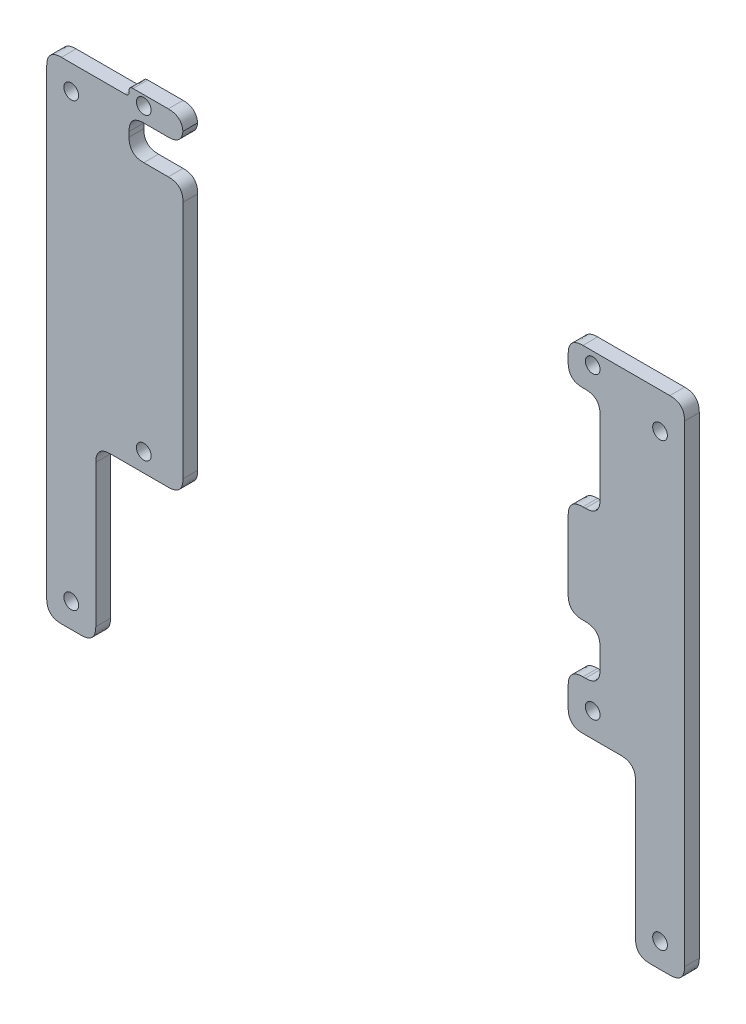
SolidWorks part; units mm, degrees
ref_plane "Front Plane" through (0, 0, 0) normal (0, 0, 1) x (1, 0, 0)
ref_plane "Top Plane" through (0, 0, 0) normal (0, 1, 0) x (1, 0, 0)
ref_plane "Right Plane" through (0, 0, 0) normal (1, 0, 0) x (0, 0, -1)
sketch "Sketch1" plane through (0, 0, 0) normal (0, 0, 1) x (1, 0, 0)
  line L0 (-89.3392, 6.8) -> (-78.3392, 6.8)
  line L1 (-78.3392, 6.8) -> (-78.3392, 1.8)
  line L2 (-78.3392, -60) -> (-96.1192, -60)
  line L3 (-96.1192, -60) -> (-96.1192, -95)
  line L4 (-96.1192, -95) -> (-106.1192, -95)
  line L5 (-106.1192, -95) -> (-106.1192, 5)
  line L10 (23.8808, -95) -> (23.8808, 7.3)
  line L15 (0.1608, -61.2) -> (13.8808, -61.2)
  line L16 (13.8808, -61.2) -> (13.8808, -95)
  line L21 (0.1608, -51.2) -> (0.1608, -61.2)
  line L22 (13.8808, -95) -> (23.8808, -95)
  line L25 (0.1608, -51.2) -> (6.6608, -51.2)
  line L29 (0.1608, 7.3) -> (0.1608, -0.2)
  line L30 (0.1608, -41.2) -> (6.6608, -41.2)
  line L33 (-89.3392, 6.8) -> (-89.3392, 5)
  line L34 (6.6608, -41.2) -> (6.6608, -51.2)
  line L35 (-89.3392, 5) -> (-106.1192, 5)
  line L37 (23.8808, 7.3) -> (0.1608, 7.3)
  line L39 (0.1608, -21.2) -> (6.6608, -21.2)
  line L40 (6.6608, -21.2) -> (6.6608, -0.2)
  line L41 (6.6608, -0.2) -> (0.1608, -0.2)
  line L42 (0.1608, -21.2) -> (0.1608, -41.2)
  line L43 (-78.3392, 1.8) -> (-89.3392, 1.8)
  line L44 (-89.3392, 1.8) -> (-89.3392, -5.2)
  line L45 (-89.3392, -5.2) -> (-78.3392, -5.2)
  line L46 (-78.3392, -5.2) -> (-78.3392, -60)
  circle A1 centre (18.8808, 0) radius 1.5
  circle A2 centre (18.8808, -90) radius 1.5
  circle A3 centre (5.1608, -56.2) radius 1.5
  circle A4 centre (-101.1192, 0) radius 1.5
  circle A5 centre (-101.1192, -90) radius 1.5
  circle A6 centre (-86.3392, 4.8) radius 1.5
  circle A7 centre (-86.3392, -56.2) radius 1.5
  circle A8 centre (5.1608, 4.8) radius 1.5
  dimension "D24" = 3
  dimension "D3" = 2.5
  dimension "D4" = 90
  dimension "D5" = 15
  dimension "D6" = 120
  dimension "D7" = 35
  dimension "D8" = 5
  dimension "D9" = 5
  dimension "D10" = 5
  dimension "D11" = 8
  dimension "D12" = 56
  dimension "D13" = 30
  dimension "D14" = 2
  dimension "D15" = 5
  dimension "D16" = 5
  dimension "D17" = 5
  dimension "D18" = 61
  dimension "D19" = 4.8
  dimension "D20" = 5
  dimension "D21" = 3
  dimension "D22" = 91.5
  dimension "D23" = 13.72
  dimension "D25" = 5
  dimension "D26" = 5
  dimension "D27" = 7
extrude "Boss-Extrude1" add sketch "Sketch1" along normal blind 3
fillet "Fillet1" radius 3 14 edges at (23.8808, -95, 1.5) (13.8808, -95, 1.5) (13.8808, -61.2, 1.5) (0.1608, -61.2, 1.5) (0.1608, -51.2, 1.5) (6.6608, -51.2, 1.5) (6.6608, -41.2, 1.5) (0.1608, -41.2, 1.5) (23.8808, 7.3, 1.5) (0.1608, 7.3, 1.5) (0.1608, -0.2, 1.5) (6.6608, -0.2, 1.5) (6.6608, -21.2, 1.5) (0.1608, -21.2, 1.5) conic rho 0.5
fillet "Fillet2" radius 3 10 edges at (-106.1192, 5, 1.5) (-78.3392, 6.8, 1.5) (-96.1192, -60, 1.5) (-96.1192, -95, 1.5) (-106.1192, -95, 1.5) (-78.3392, -60, 1.5) (-78.3392, -5.2, 1.5) (-89.3392, -5.2, 1.5) (-89.3392, 1.8, 1.5) (-78.3392, 1.8, 1.5) conic rho 0.5
fillet "Fillet3" radius 0.8 2 edges at (-89.3392, 5, 1.5) (-89.3392, 6.8, 1.5) conic rho 0.5
